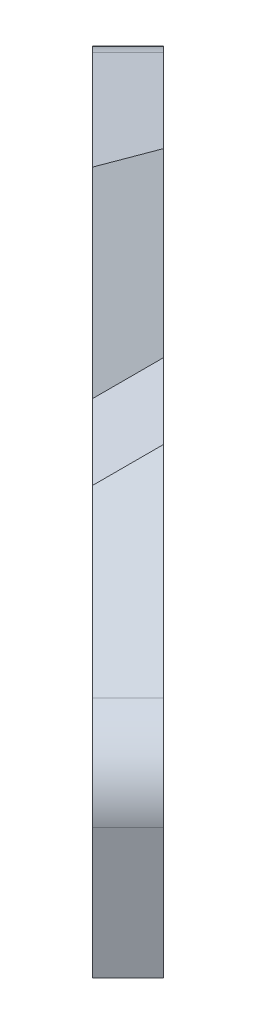
SolidWorks part; units mm, degrees
material "12Х18Н10Т ГОСТ 4543-71"
ref_plane "Спереди" through (0, 0, 0) normal (0, 0, 1) x (1, 0, 0)
ref_plane "Сверху" through (0, 0, 0) normal (0, 1, 0) x (1, 0, 0)
ref_plane "Справа" through (0, 0, 0) normal (1, 0, 0) x (0, 0, -1)
sketch "Эскиз1" plane through (0, 0, 0) normal (0, 0, 1) x (1, 0, 0)
  line L0 (0, 0) -> (0, 30)
  line L1 (0, 30) -> (39.675, 30)
  line L2 (39.675, 30) -> (59.675, 10)
  line L3 (59.675, 10) -> (74.675, 10)
  line L4 (74.675, 10) -> (94.675, 30)
  line L5 (94.675, 30) -> (134.35, 30)
  line L6 (134.35, 30) -> (134.35, 0)
  line L7 (134.35, 0) -> (0, 0)
  dimension "D1" = 134.35
  dimension "D2" = 39.675
  dimension "D3" = 39.675
  dimension "D4" = 45
  dimension "D5" = 45
  dimension "D6" = 15
  dimension "D7" = 20
  dimension "D8" = 30
extrude "Бобышка-Вытянуть1" add sketch "Эскиз1" along normal blind 134.35
sketch "Эскиз2" plane through (0, 0, 0) normal (0, -1, 0) x (1, 0, 0)
  line L0 (127.2789, 134.35) -> (0, 7.0711)
  line L1 (0, 134.35) -> (134.35, 134.35) construction
  line L2 (0, 134.35) -> (0, 0) construction
  line L3 (0, 7.0711) -> (7.0711, 0)
  line L4 (0, 0) -> (134.35, 0) construction
  line L5 (7.0711, 0) -> (134.35, 127.2789)
  line L6 (134.35, 134.35) -> (134.35, 0) construction
  line L7 (134.35, 127.2789) -> (127.2789, 134.35)
  dimension "D1" = 10
extrude "Вырез-Вытянуть1" cut sketch "Эскиз2" against normal through all flip side to cut
sketch "Эскиз4" plane through (-3.5355, 0, 3.5355) normal (-0.7071, 0, 0.7071) x (0.7071, 0, 0.7071)
  line L0 (61.1089, 30) -> (16.126, 17.9744)
  line L1 (5, 30) -> (5, 0) construction
  line L2 (5, 3.4833) -> (5, 0)
  line L3 (5, 0) -> (184.9996, 0)
  line L4 (184.9996, 0) -> (184.9996, 3.4697)
  line L5 (184.9996, 30) -> (184.9996, 0) construction
  line L6 (173.8571, 17.9652) -> (128.6343, 30)
  line L7 (61.1089, 30) -> (5, 30) construction
  arc A0 (184.9996, 3.4697) -> (173.8571, 17.9652) centre (169.9996, 3.4697) ccw
  arc A1 (5, 3.4833) -> (16.126, 17.9744) centre (20, 3.4833) cw
  point P19 (184.9996, 15)
  point P22 (5, 15)
  dimension "D3" = 15
  dimension "D1" = 15
  dimension "D2" = 14.967
extrude "Вырез-Вытянуть2" cut sketch "Эскиз4" against normal through all and the other way through all flip side to cut
sketch "Эскиз5" plane through (0, 0, 0) normal (0, -1, 0) x (1, 0, 0)
  line L4 (134.35, 127.2789) -> (127.2789, 134.35)
  line L5 (127.2789, 134.35) -> (0, 7.0711)
  line L6 (0, 7.0711) -> (7.0711, 0)
  line L7 (7.0711, 0) -> (134.35, 127.2789)
  line L8 (134.35, 127.2789) -> (127.2789, 134.35)
  line L9 (127.2789, 134.35) -> (0, 7.0711)
  line L10 (0, 7.0711) -> (7.0711, 0)
  line L11 (7.0711, 0) -> (134.35, 127.2789)
  dimension "D1" = 0
extrude "Бобышка-Вытянуть2" add sketch "Эскиз5" along normal blind 22.5
ref_plane "Плоскость1" through (0, 0, 0) normal (-0.7071, 0, 0.7071) x (0.7071, 0, 0.7071)
ref_plane "Плоскость2" through (67.175, 0, 67.175) normal (0.7071, 0, 0.7071) x (0.7071, 0, -0.7071)
